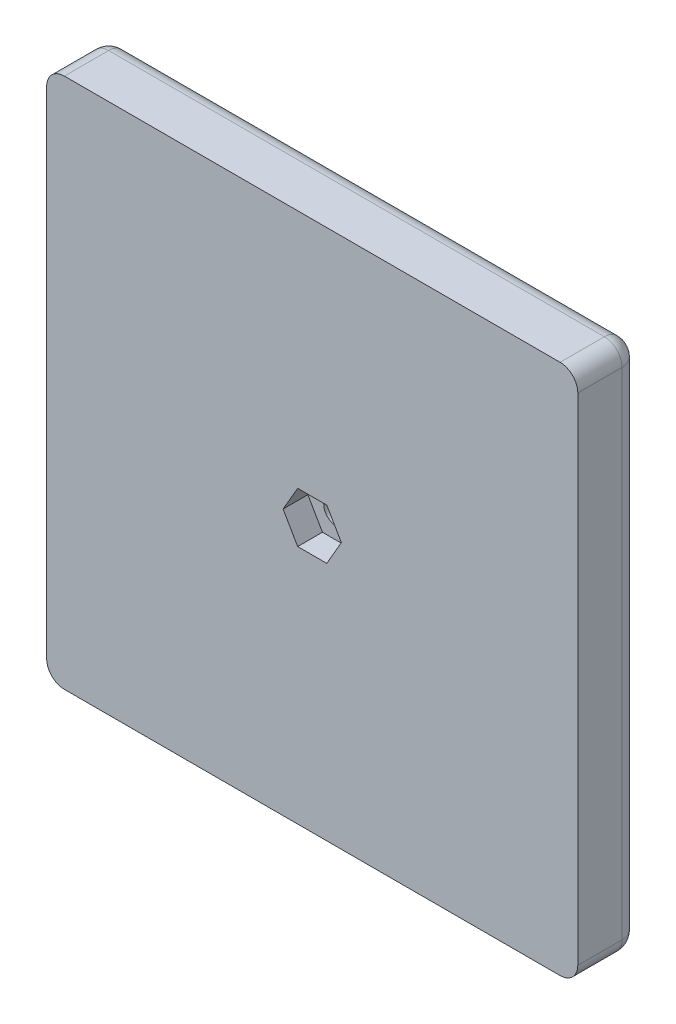
SolidWorks part; units mm, degrees
ref_plane "Plano frontal" through (0, 0, 0) normal (0, 0, 1) x (1, 0, 0)
ref_plane "Plano superior" through (0, 0, 0) normal (0, 1, 0) x (1, 0, 0)
ref_plane "Plano direito" through (0, 0, 0) normal (1, 0, 0) x (0, 0, -1)
sketch "Esboço1" plane through (0, 0, 0) normal (0, 0, 1) x (1, 0, 0)
  line L1 (-11.5, -11.5) -> (11.5, -11.5)
  line L2 (-11.5, -11.5) -> (-11.5, 11.5)
  line L3 (-11.5, 11.5) -> (11.5, 11.5)
  line L4 (11.5, -11.5) -> (11.5, 11.5)
  line L5 (-11.5, -11.5) -> (11.5, 11.5) construction
  line L6 (-11.5, 11.5) -> (11.5, -11.5) construction
  point P0 (0, 0)
  dimension "D1" = 23
  dimension "D2" = 23
extrude "Ressalto-extrusão1" add sketch "Esboço1" along normal blind 10.25
sketch "Esboço2" plane through (0, 0, 0) normal (0, 0, -1) x (-1, 0, 0)
  circle A0 centre (0, 0) radius 4.2
  dimension "D1" = 8.4
extrude "Corte-extrusão1" cut sketch "Esboço2" against normal up to next
sketch "Esboço3" plane through (0, 0, 10.25) normal (0, 0, 1) x (1, 0, 0)
  line L1 (30, -30) -> (-30, -30)
  line L2 (30, -30) -> (30, 30)
  line L3 (30, 30) -> (-30, 30)
  line L4 (-30, -30) -> (-30, 30)
  line L5 (30, -30) -> (-30, 30) construction
  line L6 (30, 30) -> (-30, -30) construction
  point P0 (0, 0)
  dimension "D1" = 60
  dimension "D2" = 60
extrude "Ressalto-extrusão2" add sketch "Esboço3" along normal blind 7
sketch "Esboço4" plane through (0, 0, 10.25) normal (0, 0, -1) x (-1, 0, 0)
  circle A0 centre (0, 0) radius 1.5
  dimension "D1" = 3
extrude "Corte-extrusão2" cut sketch "Esboço4" against normal up to next
sketch "Esboço5" plane through (0, 0, 17.25) normal (0, 0, 1) x (1, 0, 0)
  line L1 (3.2909, 0) -> (1.6454, 2.85)
  line L2 (1.6454, 2.85) -> (-1.6454, 2.85)
  line L3 (-1.6454, 2.85) -> (-3.2909, 0)
  line L4 (-3.2909, 0) -> (-1.6454, -2.85)
  line L5 (-1.6454, -2.85) -> (1.6454, -2.85)
  line L6 (1.6454, -2.85) -> (3.2909, 0)
  circle A0 centre (0, 0) radius 2.85 construction
  dimension "D1" = 5.7
extrude "Corte-extrusão3" cut sketch "Esboço5" against normal blind 2.8
fillet "Filete1" radius 2 4 edges at (30, 0, 10.25) (0, -30, 10.25) (-30, 0, 10.25) (0, 30, 10.25)
fillet "Filete2" radius 2 8 edges at (29.4142, -29.4142, 10.8358) (29.4142, 29.4142, 10.8358) (-29.4142, 29.4142, 10.8358) (-29.4142, -29.4142, 10.8358) (30, -30, 14.75) (30, 30, 14.75) (-30, 30, 14.75) (-30, -30, 14.75)
